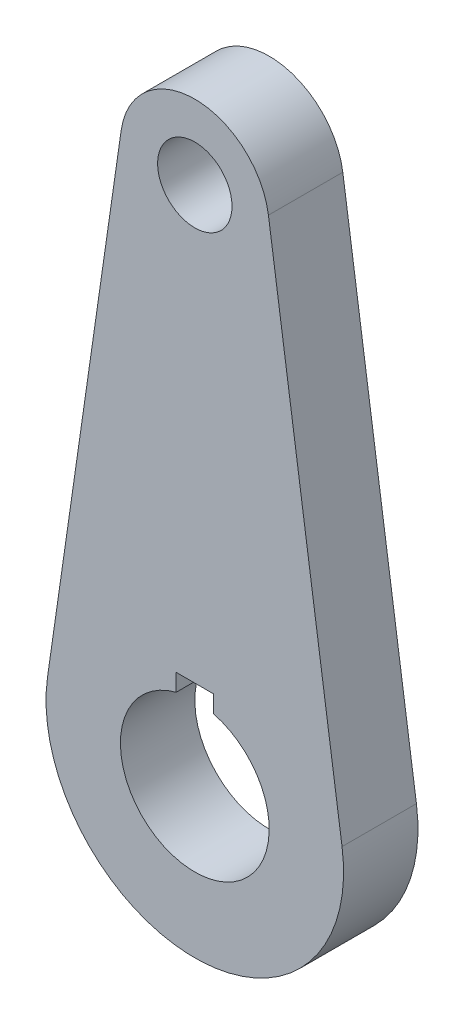
SolidWorks part; units mm, degrees
ref_plane "Front Plane" through (0, 0, 0) normal (0, 0, 1) x (1, 0, 0)
ref_plane "Top Plane" through (0, 0, 0) normal (0, 1, 0) x (1, 0, 0)
ref_plane "Right Plane" through (0, 0, 0) normal (1, 0, 0) x (0, 0, -1)
sketch "Sketch2" plane through (0, 0, 0) normal (0, 0, 1) x (1, 0, 0)
  line L0 (-19.7949, 2.8571) -> (-9.8974, 71.4286)
  line L1 (9.8974, 71.4286) -> (19.7949, 2.8571)
  line L2 (-2.5, 9.6825) -> (-2.5, 12)
  line L3 (-2.5, 12) -> (2.5, 12)
  line L4 (2.5, 12) -> (2.5, 9.6825)
  arc A0 (-19.7949, 2.8571) -> (19.7949, 2.8571) centre (0, 0) ccw
  arc A1 (-2.5, 9.6825) -> (2.5, 9.6825) centre (0, 0) ccw
  arc A2 (9.8974, 71.4286) -> (-9.8974, 71.4286) centre (0, 70) ccw
  circle A3 centre (0, 70) radius 5
  point P12 (0, 12)
  dimension "D1" = 20
  dimension "D2" = 40
  dimension "D3" = 10
  dimension "D4" = 20
  dimension "D5" = 70
  dimension "D6" = 12
  dimension "D7" = 5
extrude "Boss-Extrude1" add sketch "Sketch2" along normal blind 10
sketch "Sketch3" plane through (0, 0, 10) normal (0, 0, 1) x (1, 0, 0)
  circle A0 centre (0, 70) radius 10
  arc A1 (9.8974, 71.4286) -> (-9.8974, 71.4286) centre (0, 70) ccw construction
  circle A2 centre (0, 70) radius 5
  circle A3 centre (0, 70) radius 5 construction
extrude "Boss-Extrude2" add sketch "Sketch3" along normal blind 76.2
extrude "Boss-Extrude3" add sketch "Sketch2<2>" along normal blind 22 from surface starting at face at (10, 70, 86.2)
sketch "Sketch2<2>" plane through (0, 0, 0) normal (0, 0, 1) x (1, 0, 0) same geometry as "Sketch2"
sketch "Sketch5" plane through (0, 0, 108.2) normal (0, 0, 1) x (1, 0, 0)
  circle A0 centre (0, 0) radius 65
  dimension "D1" = 130
extrude "Boss-Extrude4" add sketch "Sketch5" against normal up to surface (22 mm away) up to face at (0, 5.9206, 86.2)
sketch "Sketch6" plane through (0, 0, 108.2) normal (0, 0, 1) x (1, 0, 0)
  circle A0 centre (0, 0) radius 55
  dimension "D1" = 110
extrude "Cut-Extrude1" cut sketch "Sketch6" against normal up to surface (22 mm away) contours A0 up to face at (0, 32.6245, 86.2)
sketch "Sketch7" plane through (0, 0, 10) normal (0, 0, 1) x (1, 0, 0)
  circle A0 centre (0, 0) radius 80
  arc A1 (9.8974, 71.4286) -> (-9.8974, 71.4286) centre (0, 70) ccw construction
extrude "Cut-Extrude2" cut sketch "Sketch7" along normal through all
